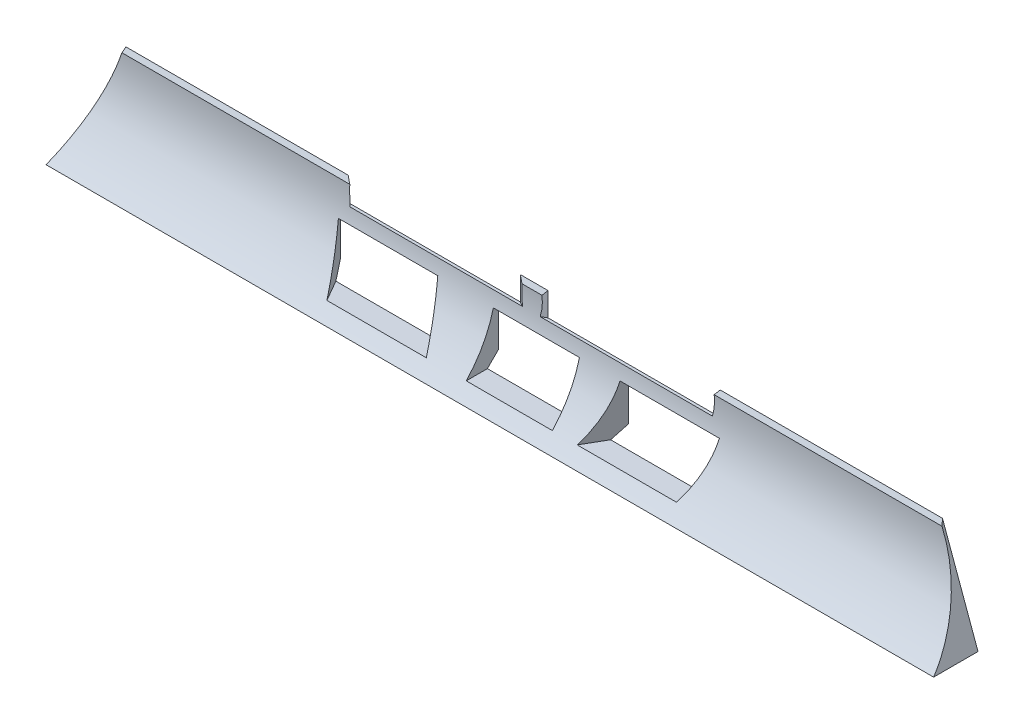
SolidWorks part; units mm, degrees
material "ABS"
ref_plane "Front Plane" through (0, 0, 0) normal (0, 0, 1) x (1, 0, 0)
ref_plane "Top Plane" through (0, 0, 0) normal (0, 1, 0) x (1, 0, 0)
ref_plane "Right Plane" through (0, 0, 0) normal (1, 0, 0) x (0, 0, -1)
sketch "Sketch1" plane through (0, 0, 0) normal (1, 0, 0) x (0, 0, -1)
  line L0 (0, 0) -> (-10, 0)
  line L1 (-10, 0) -> (0, 22)
  line L2 (0, 22) -> (0, 0)
  dimension "D1" = 10
  dimension "D2" = 22
extrude "Boss-Extrude1" add sketch "Sketch1" along normal blind 200
sketch "Sketch2" plane through (200, 0, 0) normal (1, 0, 0) x (0, 0, -1)
  line L0 (0, 22) -> (-10, 0) construction
  line L1 (-10, 0) -> (0, 0) construction
  line L2 (0, 0) -> (0, 22) construction
  line L3 (-10, 0) -> (-0.5, 20.9)
  arc A0 (-10, 0) -> (-0.5, 20.9) centre (-25.4682, 19.6401) ccw
  dimension "D3" = 25
  dimension "D1" = 0
  dimension "D2" = 0.5
extrude "Cut-Extrude1" cut sketch "Sketch2" against normal through all
sketch "Sketch4" plane through (200, 0, 0) normal (1, 0, 0) x (0, 0, -1)
  line L0 (-5, 0) -> (0, 5)
  line L1 (-10, 0) -> (0, 0) construction
  line L2 (0, 0) -> (0, 22) construction
  line L3 (0, 5) -> (0, 0)
  line L4 (0, 0) -> (-5, 0)
  dimension "D1" = 5
  dimension "D2" = 5
extrude "Cut-Extrude2" cut sketch "Sketch4" against normal through all
sketch "Sketch5" plane through (0, 0, 0) normal (0, 0, -1) x (-1, 0, 0)
  line L0 (0, 0) -> (-200, 0) construction
  line L1 (-200, 5) -> (-197, 5)
  line L2 (-200, 5) -> (-200, 0)
  line L3 (-200, 0) -> (-197, 0)
  line L4 (-197, 5) -> (-197, 0)
  dimension "D1" = 3
extrude "Boss-Extrude2" add sketch "Sketch5" against normal up to surface up to face at (100, 2.5, 2.5)
ref_plane "Plane1" through (100, 0, 0) normal (1, 0, 0) x (0, 0, -1)
sketch "Sketch6" plane through (0, 0, 0) normal (0, 0, -1) x (-1, 0, 0)
  line L0 (-200, 22) -> (-191.9927, 22)
  line L1 (-200, 22) -> (0, 22) construction
  line L2 (-191.9927, 22) -> (-200, 0)
  line L3 (-200, 22) -> (-200, 0)
  dimension "D1" = 20
extrude "Cut-Extrude3" cut sketch "Sketch6" against normal through all
mirror "Mirror2" about plane through (100, 0, 0) normal (1, 0, 0) of "Cut-Extrude3", "Boss-Extrude2"
sketch "Sketch8" plane through (0, 0, 0) normal (0, 0, -1) x (-1, 0, 0)
  line L1 (-169.1734, 11.1) -> (-170.9632, 8)
  line L2 (-170.9632, 8) -> (-169.1734, 4.9)
  line L3 (-169.1734, 4.9) -> (-165.5938, 4.9)
  line L4 (-165.5938, 4.9) -> (-163.804, 8)
  line L5 (-163.804, 8) -> (-165.5938, 11.1)
  line L6 (-165.5938, 11.1) -> (-169.1734, 11.1)
  line L7 (-167.8316, 0) -> (-159.8316, 0) construction
  line L8 (-168.8836, 10.465) -> (-168.8836, 5.465) construction
  circle A2 centre (-167.3836, 8) radius 3.1 construction
  point P13 (-167.3836, 11.1)
  dimension "D1" = 6.2
  dimension "D2" = 1.5
  dimension "D3" = 8
extrude "Cut-Extrude4" cut sketch "Sketch8" against normal blind 1.8 contours L5 L6 L1 L2 L3 L4 | L1 L2 L3 L4 L5 L6 region at (167.3836, 8, 0)
sketch "Sketch9" plane through (0, 0, 0) normal (0, 0, 1) x (1, 0, 0)
  line L1 (93.9918, 4.465) -> (109.3918, 4.465)
  line L2 (93.9918, 4.465) -> (93.9918, 11.665)
  line L3 (93.9918, 11.665) -> (109.3918, 11.665)
  line L4 (109.3918, 4.465) -> (109.3918, 11.665)
  line L8 (91.9918, 13.665) -> (111.3918, 13.665)
  line L9 (111.3918, 2.465) -> (111.3918, 13.665)
  line L10 (91.9918, 2.465) -> (111.3918, 2.465)
  line L11 (91.9918, 2.465) -> (91.9918, 13.665)
  dimension "D1" = 2
extrude "Cut-Extrude6" cut sketch "Sketch9" along normal through all contours L11 L10 L9 L8 L4 L1 L2 L3 | L2 L1 L4 L3 region at (101.6918, 13.441, 0)
ref_plane "Plane2" through (32.58, 0, -56.4302) normal (-0.5, 0, 0.866) x (0.866, 0, 0.5)
sketch "Sketch10" plane through (32.58, 0, -56.4302) normal (-0.5, 0, 0.866) x (0.866, 0, 0.5)
  line L0 (104.9771, 13.665) -> (124.3771, 13.665)
  line L1 (106.9771, 4.465) -> (122.3771, 4.465)
  line L2 (106.9771, 4.465) -> (106.9771, 11.665)
  line L3 (106.9771, 11.665) -> (122.3771, 11.665)
  line L4 (122.3771, 4.465) -> (122.3771, 11.665)
  line L5 (124.3771, 2.465) -> (124.3771, 13.665)
  line L6 (104.9771, 2.465) -> (124.3771, 2.465)
  line L7 (104.9771, 2.465) -> (104.9771, 13.665)
  dimension "D1" = 2
extrude "Cut-Extrude8" cut sketch "Sketch10" along normal blind 15.8 and the other way blind 6.8 contours L1 L4 L3 L2 | L7 L6 L5 L0 L4 L1 L2 L3 region at (131.8933, 13.441, 0.9083) region at (131.8933, 8.065, 0.9083)
ref_plane "Plane3" through (117.0017, 0, -67.551) normal (-0.866, 0, 0.5) x (0.5, 0, 0.866)
sketch "Sketch11" plane through (117.0017, 0, -67.551) normal (-0.866, 0, 0.5) x (0.5, 0, 0.866)
  line L0 (70.9597, 29.465) -> (70.9597, 16.665)
  line L1 (68.9597, 27.465) -> (53.5597, 27.465)
  line L2 (68.9597, 27.465) -> (68.9597, 18.665)
  line L3 (68.9597, 18.665) -> (53.5597, 18.665)
  line L4 (53.5597, 27.465) -> (53.5597, 18.665)
  line L5 (70.9597, 16.665) -> (51.5597, 16.665)
  line L6 (51.5597, 29.465) -> (51.5597, 16.665)
  line L7 (53.5597, 27.465) -> (53.5597, 20.265) construction
  line L8 (48.0097, 18.665) -> (74.5097, 18.665) construction
  line L9 (70.9597, 29.465) -> (51.5597, 29.465)
  dimension "D1" = 2
extrude "Cut-Extrude9" cut sketch "Sketch11" along normal blind 97.8 contours L1 L4 L3 L2 | L0 L9 L6 L5 L4 L1 L2 L3 region at (152.3653, 23.065, -6.2994) region at (147.6316, 23.065, -14.4985)
mirror "Mirror4" about plane through (100, 0, 0) normal (1, 0, 0) of "Cut-Extrude8", "Cut-Extrude9"
mirror "Mirror5" about plane through (100, 0, 0) normal (1, 0, 0) of "Cut-Extrude4"
